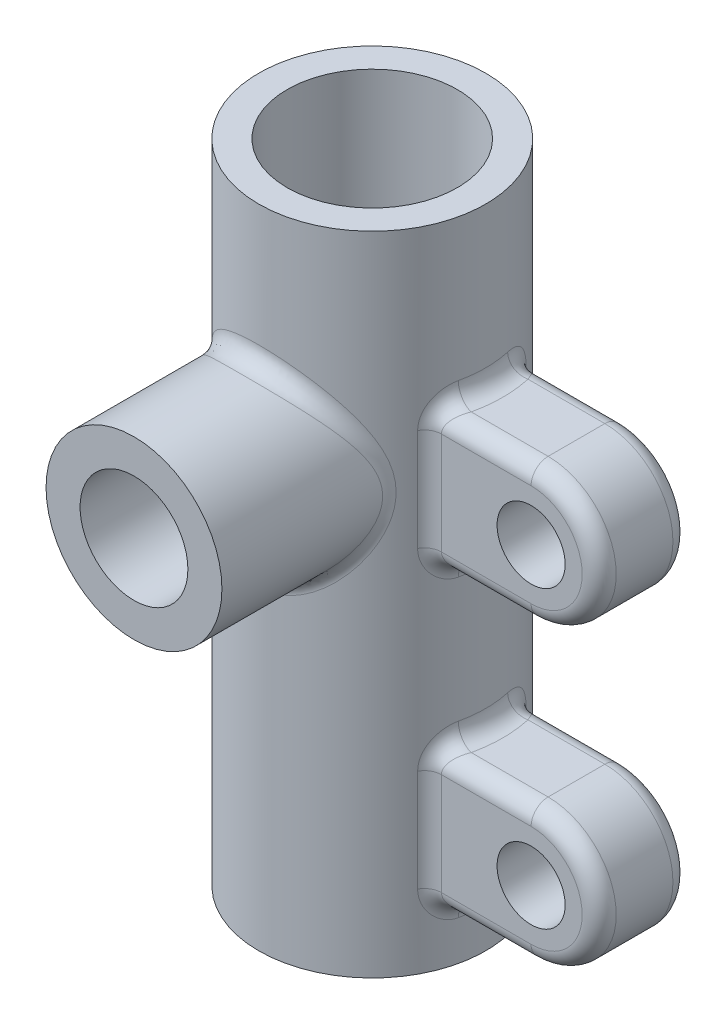
SolidWorks part; units mm, degrees
material "Duranickel(R) 301"
ref_plane "Front Plane" through (0, 0, 0) normal (0, 0, 1) x (1, 0, 0)
ref_plane "Top Plane" through (0, 0, 0) normal (0, 1, 0) x (1, 0, 0)
ref_plane "Right Plane" through (0, 0, 0) normal (1, 0, 0) x (0, 0, -1)
sketch "Sketch1" plane through (0, 0, 0) normal (0, 1, 0) x (1, 0, 0)
  circle A0 centre (0, 0) radius 20
  dimension "D1" = 40
extrude "Boss-Extrude1" add sketch "Sketch1" along normal blind 40 and the other way blind 74
sketch "Sketch2" plane through (0, 0, 0) normal (0, 0, 1) x (1, 0, 0)
  circle A0 centre (0, 0) radius 15.5
  dimension "D1" = 31
extrude "Boss-Extrude2" add sketch "Sketch2" along normal blind 42
sketch "Sketch3" plane through (0, 0, 0) normal (0, 0, 1) x (1, 0, 0)
  line L0 (0, 12) -> (0, -12)
  line L1 (0, -12) -> (36, -12)
  line L2 (36, 12) -> (0, 12)
  line L3 (22, 0) -> (-22, 0) construction
  arc A0 (36, -12) -> (36, 12) centre (36, 0) ccw
  circle A1 centre (36, 0) radius 6
  dimension "D2" = 36
  dimension "D3" = 12
  dimension "D1" = 24
extrude "Boss-Extrude3" add sketch "Sketch3" along normal mid plane 16
pattern_linear "LPattern1" count 2 spacing 52 along (0, -1, 0) of "Boss-Extrude3"
sketch "Sketch4" plane through (0, 40, 0) normal (0, 1, 0) x (1, 0, 0)
  circle A0 centre (0, 0) radius 15
  dimension "D1" = 30
extrude "Cut-Extrude1" cut sketch "Sketch4" against normal through all
sketch "Sketch5" plane through (0, 0, 42) normal (0, 0, 1) x (1, 0, 0)
  circle A0 centre (0, 0) radius 9.5
  dimension "D1" = 19
extrude "Cut-Extrude2" cut sketch "Sketch5" against normal up to next
fillet "Fillet1" radius 3 12 edges at (27.1652, -64, -8) (48, -52, -8) (27.1652, -64, 8) (48, -52, 8) (27.1652, -12, -8) (48, 0, -8) (27.1652, -12, 8) (48, 0, 8) (27.1652, -40, -8) (27.1652, -40, 8) (27.1652, 12, -8) (27.1652, 12, 8)
fillet "Fillet2" radius 3 17 edges at (18.5713, -41.2315, 7.4233) (18.3303, -52, 8) (18.7615, -63.2978, 6.9287) (20, -64, 0) (18.5713, -62.7685, -7.4233) (18.3303, -52, -8) (18.7615, -40.7022, -6.9287) (18.5713, 10.7685, 7.4233) (18.3303, 0, 8) (18.7615, -11.2978, 6.9287) (20, -12, 0) (18.5713, -10.7685, -7.4233) (18.3303, 0, -8) (18.7615, 11.2978, -6.9287) (20, -40, 0) (20, 12, 0) (0.6115, 15.4879, 19.9906)
